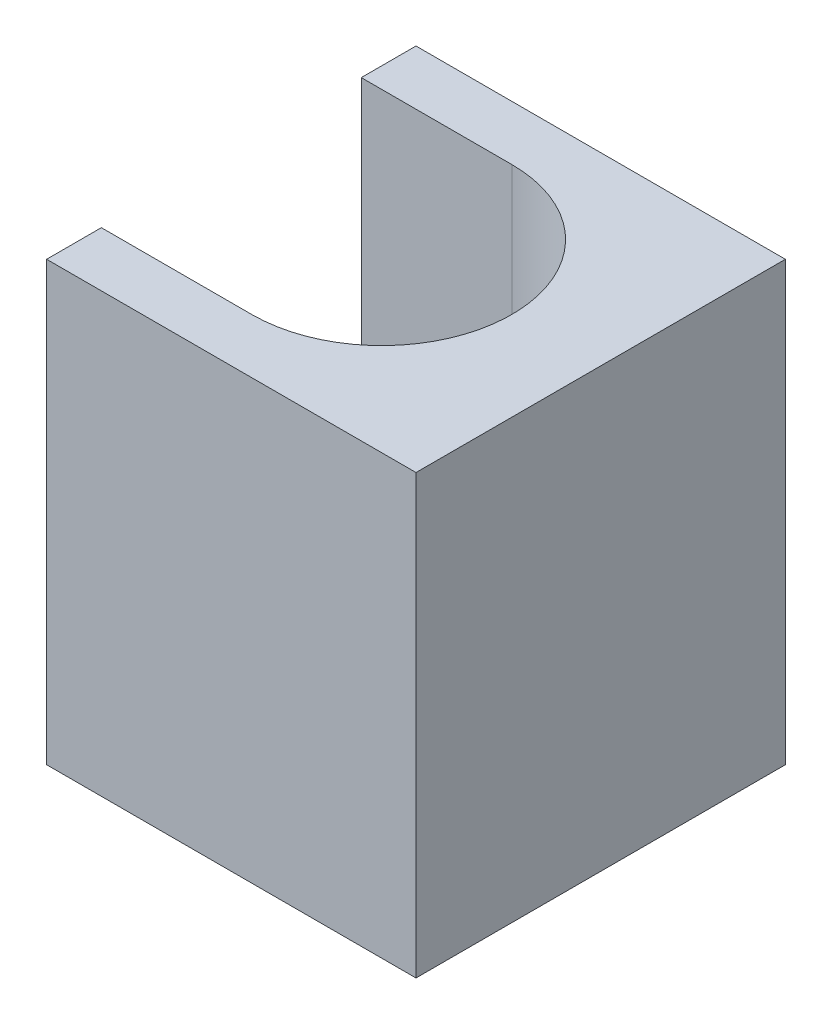
SolidWorks part; units mm, degrees
ref_plane "前视基准面" through (0, 0, 0) normal (0, 0, 1) x (1, 0, 0)
ref_plane "上视基准面" through (0, 0, 0) normal (0, 1, 0) x (1, 0, 0)
ref_plane "右视基准面" through (0, 0, 0) normal (1, 0, 0) x (0, 0, -1)
sketch "草图1" plane through (0, 0, 0) normal (0, 1, 0) x (1, 0, 0)
  line L0 (0, 0) -> (0, 9.5)
  line L1 (0, 9.5) -> (5.5, 9.5)
  line L2 (5.5, 0) -> (0, 0)
  line L3 (5.5, 9.5) -> (11.5, 9.5)
  line L4 (11.5, 9.5) -> (11.5, 0)
  line L5 (11.5, 0) -> (5.5, 0)
  line L6 (5.5, -2) -> (0, -2)
  line L7 (0, 0) -> (0, -2)
  line L8 (0, 11.5) -> (5.5, 11.5)
  line L9 (5.5, 11.5) -> (13.5, 11.5)
  line L10 (13.5, 11.5) -> (13.5, -2)
  line L11 (13.5, -2) -> (5.5, -2)
  line L12 (-2, -2) -> (-2, 11.5) construction
  line L13 (0, 9.5) -> (0, 11.5)
  line L14 (5.5, -2) -> (-2, -2) construction
  line L16 (-2, 11.5) -> (5.5, 11.5) construction
  arc A0 (5.5, 9.5) -> (5.5, 0) centre (5.5, 4.75) cw
  circle A1 centre (5.5, 4.75) radius 3.5
  dimension "D5" = 7
  dimension "D1" = 9.5
  dimension "D2" = 5.5
  dimension "D3" = 11.5
  dimension "D4" = 2
extrude "凸台-拉伸2" add sketch "草图1" along normal blind 16 contours L13 L1 L3 L4 L5 L2 L7 L6 L11 L10 L9 L8 | L3 A0 L5 L4 | A0 L1 L0 L2 A1
extrude "切除-拉伸6" cut sketch "草图1<7>" along normal blind 4 from offset 2 contours A0 L1 L0 L2 A1 | L3 A0 L5 L4 region at (0.1398, 0, -4.75) region at (10.3624, 0, -4.75)
sketch "草图1<7>" plane through (0, 0, 0) normal (0, 1, 0) x (1, 0, 0) same geometry as "草图1"
extrude "切除-拉伸8" cut sketch "草图1<9>" along normal blind 14 from offset 2 contours A0 L1 L0 L2 A1 region at (0.1398, 0, -4.75)
sketch "草图1<9>" plane through (0, 0, 0) normal (0, 1, 0) x (1, 0, 0) same geometry as "草图1"
